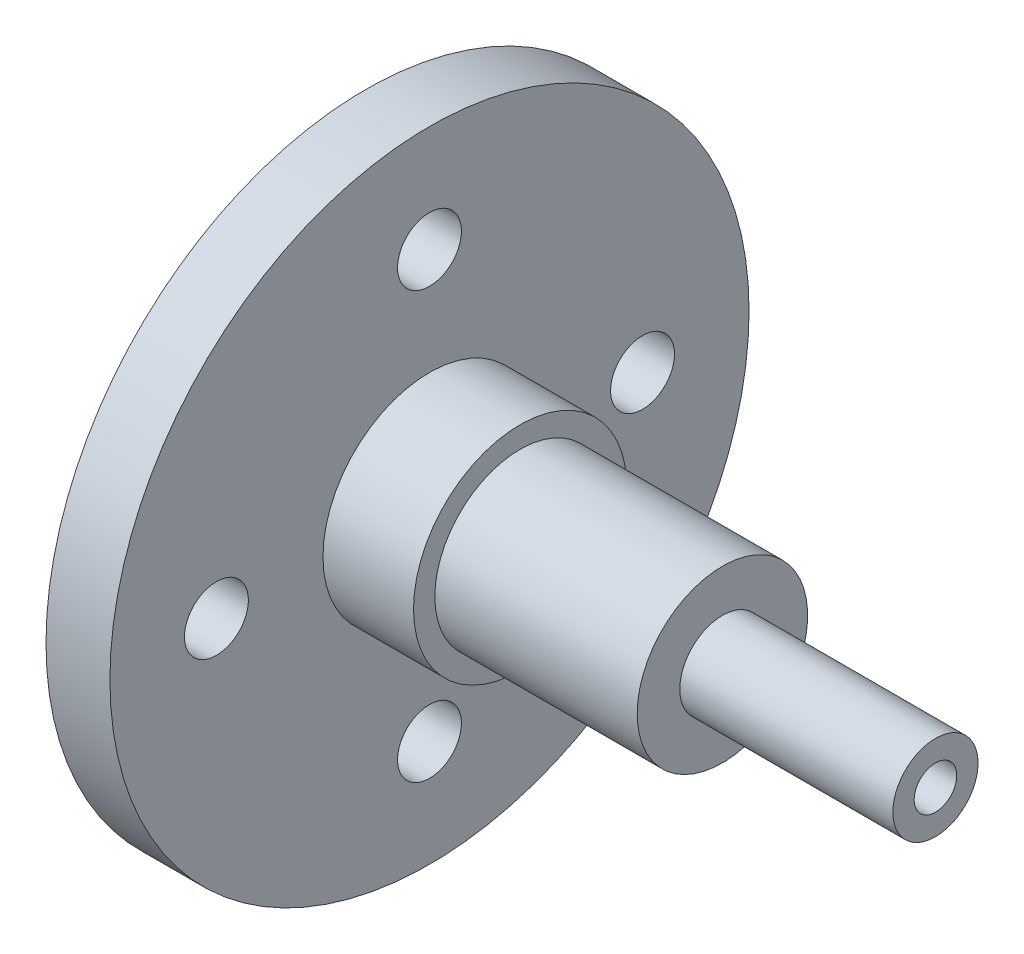
SolidWorks part; units mm, degrees
ref_plane "Front Plane" through (0, 0, 0) normal (0, 0, 1) x (1, 0, 0)
ref_plane "Top Plane" through (0, 0, 0) normal (0, 1, 0) x (1, 0, 0)
ref_plane "Right Plane" through (0, 0, 0) normal (1, 0, 0) x (0, 0, -1)
sketch "Sketch1" plane through (0, 0, 0) normal (0, 0, 1) x (1, 0, 0)
  line L0 (-13.375, 0) -> (13.375, 0) construction
  line L7 (-13.375, 1) -> (-13.375, 15)
  line L10 (-13.375, 15) -> (-10.375, 15)
  line L11 (-10.375, 15) -> (-10.375, 5)
  line L12 (-10.375, 5) -> (-6.125, 5)
  line L13 (-6.125, 5) -> (-6.125, 4)
  line L14 (-6.125, 4) -> (3.375, 4)
  line L15 (3.375, 4) -> (3.375, 2)
  line L16 (3.375, 2) -> (13.375, 2)
  line L17 (13.375, 2) -> (13.375, 1)
  line L18 (-1.375, 4) -> (-1.375, 0) construction
  line L19 (13.375, 1) -> (-13.375, 1)
  point P3 (0, 0)
  point P18 (-21.0299, 0)
  point P19 (-21.0299, 0)
  point P20 (0, 0)
  point P21 (0, 0)
  point P22 (21.951, 1.5079)
  point P23 (-11.875, 15)
  dimension "D1" = 9.5
  dimension "D2" = 12
  dimension "D3" = 3
  dimension "D4" = 8
  dimension "D5" = 10
  dimension "D6" = 30
  dimension "D7" = 2
  dimension "D8" = 4
  dimension "D9" = 10
revolve "Revolve1" add sketch "Sketch1" angle 360 about L0
sketch "Sketch2" plane through (-10.375, 0, 0) normal (1, 0, 0) x (0, 0, -1)
  line L0 (0, 0) -> (0, 10) construction
  circle A0 centre (0, 10) radius 1.5
  circle A1 centre (10, 0) radius 1.5
  circle A2 centre (0, -10) radius 1.5
  circle A3 centre (-10, 0) radius 1.5
  point P13 (0, 0)
  dimension "D1" = 3
  dimension "D2" = 10
  dimension "D4" = 10
  dimension "D5" = 10
  dimension "D3" = 4
extrude "Cut-Extrude1" cut sketch "Sketch2" against normal through all
